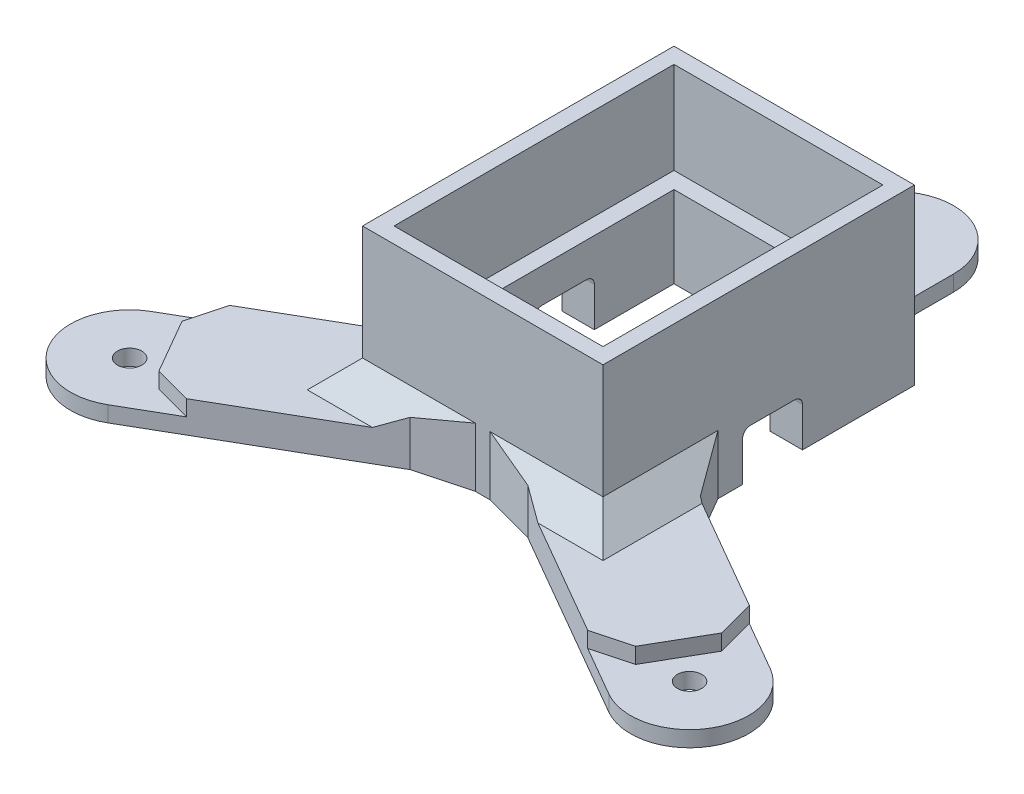
SolidWorks part; units mm, degrees
ref_plane "Front Plane" through (0, 0, 0) normal (0, 0, 1) x (1, 0, 0)
ref_plane "Top Plane" through (0, 0, 0) normal (0, 1, 0) x (1, 0, 0)
ref_plane "Right Plane" through (0, 0, 0) normal (1, 0, 0) x (0, 0, -1)
sketch "Sketch1" plane through (0, 0, 0) normal (0, 1, 0) x (1, 0, 0)
  line L0 (15.25, 19.75) -> (-15.25, 19.75)
  line L1 (13.25, -17.75) -> (-13.25, -17.75)
  line L2 (13.25, -17.75) -> (13.25, 17.75)
  line L3 (13.25, 17.75) -> (-13.25, 17.75)
  line L4 (-13.25, -17.75) -> (-13.25, 17.75)
  line L5 (13.25, -17.75) -> (-13.25, 17.75) construction
  line L6 (13.25, 17.75) -> (-13.25, -17.75) construction
  line L7 (-15.25, -19.75) -> (-15.25, 19.75)
  line L8 (15.25, -19.75) -> (-15.25, -19.75)
  line L9 (15.25, -19.75) -> (15.25, 19.75)
  point P0 (0, 0)
  dimension "D1" = 35.5
  dimension "D2" = 26.5
  dimension "D3" = 2
extrude "Boss-Extrude1" add sketch "Sketch1" along normal blind 22
sketch "Sketch3" plane through (0, 0, 0) normal (0, -1, 0) x (1, 0, 0)
  line L1 (-13.25, 17.75) -> (13.25, 17.75)
  line L2 (-13.25, 17.75) -> (-13.25, -17.75)
  line L3 (-13.25, -17.75) -> (13.25, -17.75)
  line L4 (13.25, 17.75) -> (13.25, -17.75)
  line L12 (-11.15, 15.65) -> (-11.15, -15.65)
  line L13 (11.15, 15.65) -> (-11.15, 15.65)
  line L14 (11.15, -15.65) -> (11.15, 15.65)
  line L15 (-11.15, -15.65) -> (11.15, -15.65)
  line L16 (-11.15, 15.65) -> (-11.15, -15.65)
  line L17 (11.15, 15.65) -> (-11.15, 15.65)
  line L18 (11.15, -15.65) -> (11.15, 15.65)
  line L19 (-11.15, -15.65) -> (11.15, -15.65)
  dimension "D1" = 2.1
extrude "Boss-Extrude3" add sketch "Sketch3" against normal blind 10.35
sketch "Sketch4" plane through (0, 22, 0) normal (0, 1, 0) x (1, 0, 0)
  line L1 (-15.25, 19.75) -> (-15.25, -19.75) construction
  line L2 (0, -8.53) -> (-35.507, -29.03) construction
  line L6 (-31.757, -35.5252) -> (-4.4336, -19.75)
  line L7 (-15.25, -19.75) -> (15.25, -19.75) construction
  line L10 (-15.25, -8.6743) -> (-39.257, -22.5348)
  line L11 (0, 0) -> (0, -8.53) construction
  line L12 (15.25, 19.75) -> (-15.25, 19.75) construction
  line L13 (-7.5, 19.75) -> (7.5, 19.75)
  line L14 (-7.5, 19.75) -> (-7.5, 32.47)
  line L15 (-7.5, 32.47) -> (7.5, 32.47) construction
  line L16 (7.5, 19.75) -> (7.5, 32.47)
  line L17 (-15.25, -8.6743) -> (-15.25, -19.75)
  line L19 (-15.25, -19.75) -> (-4.4336, -19.75)
  circle A1 centre (0, -8.53) radius 41 construction
  arc A3 (-7.5, 32.47) -> (7.5, 32.47) centre (0, 32.47) cw
  circle A4 centre (-35.507, -29.03) radius 1.55
  arc A6 (-39.257, -22.5348) -> (-31.757, -35.5252) centre (-35.507, -29.03) ccw
  circle A7 centre (0, 32.47) radius 1.55
  point P23 (0, 19.75)
  dimension "D1" = 120
  dimension "D2" = 82
  dimension "D4" = 15
  dimension "D5" = 3.1
  dimension "D3" = 8.53
  dimension "D6" = 15
extrude "Boss-Extrude4" add sketch "Sketch4" along normal blind 4 from surface starting at face at (0, 0, 0)
sketch "Sketch6" plane through (0, 4, 0) normal (0, 1, 0) x (1, 0, 0)
  line L1 (-2.85, 34.1154) -> (-2.85, 30.8246)
  line L2 (-2.85, 30.8246) -> (0, 29.1791)
  line L3 (0, 29.1791) -> (2.85, 30.8246)
  line L4 (2.85, 30.8246) -> (2.85, 34.1154)
  line L5 (2.85, 34.1154) -> (0, 35.7609)
  line L6 (0, 35.7609) -> (-2.85, 34.1154)
  line L7 (-35.507, -32.3209) -> (-32.657, -30.6754)
  line L8 (-32.657, -30.6754) -> (-32.657, -27.3846)
  line L9 (-32.657, -27.3846) -> (-35.507, -25.7391)
  line L10 (-35.507, -25.7391) -> (-38.357, -27.3846)
  line L11 (-38.357, -27.3846) -> (-38.357, -30.6754)
  line L12 (-38.357, -30.6754) -> (-35.507, -32.3209)
  circle A0 centre (0, 32.47) radius 2.85 construction
  circle A1 centre (-35.507, -29.03) radius 2.85 construction
  dimension "D1" = 5.7
extrude "Cut-Extrude1" cut sketch "Sketch6" against normal offset from surface (2 mm away) 2 up to face at (-7.4494, 0, -3.7687)
mirror "Mirror1" about plane through (0, 0, 0) normal (1, 0, 0) of "Cut-Extrude1", "Boss-Extrude4"
sketch "Sketch7" plane through (15.25, 0, 0) normal (1, 0, 0) x (0, 0, -1)
  line L0 (19.75, 22) -> (19.75, 0) construction
  line L1 (5.55, 0) -> (-2.05, 0)
  line L2 (5.55, 0) -> (5.55, 5)
  line L3 (4.55, 6) -> (-1.05, 6)
  line L4 (-2.05, 0) -> (-2.05, 5)
  line L6 (-8.6743, 0) -> (19.75, 0) construction
  line L7 (1.75, 6) -> (1.75, 0) construction
  arc A0 (5.55, 5) -> (4.55, 6) centre (4.55, 5) ccw
  arc A1 (-1.05, 6) -> (-2.05, 5) centre (-1.05, 5) ccw
  point P14 (5.55, 6)
  point P17 (-2.05, 6)
  dimension "D4" = 1
  dimension "D1" = 7.6
  dimension "D2" = 6
  dimension "D3" = 18
extrude "Cut-Extrude2" cut sketch "Sketch7" against normal through all
sketch "Sketch8" plane through (0, 4, 0) normal (0, 1, 0) x (1, 0, 0)
  line L0 (-35.974, -20.6394) -> (-28.474, -33.6297)
  line L1 (-15.25, -8.6743) -> (-39.257, -22.5348) construction
  line L2 (-31.757, -35.5252) -> (-4.4336, -19.75) construction
  line L3 (-35.974, -20.6394) -> (-39.257, -22.5348)
  line L4 (-31.757, -35.5252) -> (-28.474, -33.6297)
  line L5 (7.5, 19.75) -> (7.5, 32.47) construction
  line L6 (-7.5, 32.47) -> (-7.5, 19.75) construction
  line L7 (7.5, 28.6791) -> (7.5, 32.47)
  line L8 (-7.5, 32.47) -> (-7.5, 28.6791)
  line L9 (-7.5, 28.6791) -> (7.5, 28.6791)
  line L10 (0, 0) -> (0, 15.65) construction
  line L11 (-11.15, 15.65) -> (11.15, 15.65) construction
  line L12 (31.757, -35.5252) -> (28.474, -33.6297)
  line L13 (35.974, -20.6394) -> (39.257, -22.5348)
  line L14 (35.974, -20.6394) -> (28.474, -33.6297)
  arc A0 (-39.257, -22.5348) -> (-31.757, -35.5252) centre (-35.507, -29.03) ccw construction
  arc A1 (-39.257, -22.5348) -> (-31.757, -35.5252) centre (-35.507, -29.03) ccw
  arc A2 (7.5, 32.47) -> (-7.5, 32.47) centre (0, 32.47) ccw construction
  arc A3 (7.5, 32.47) -> (-7.5, 32.47) centre (0, 32.47) ccw
  arc A4 (39.257, -22.5348) -> (31.757, -35.5252) centre (35.507, -29.03) cw
  dimension "D1" = 0.5
  dimension "D2" = 0.5
extrude "Cut-Extrude3" cut sketch "Sketch8" against normal up to surface (2 mm away) up to face at (-35.507, 2, 30.58)
chamfer "Chamfer1" distance 3.5 distance2 3.5 6 edges at (7.5, 2, -19.75) (-7.5, 2, -19.75) (-15.25, 2, 8.6743) (-4.4336, 2, 19.75) (4.4336, 2, 19.75) (15.25, 2, 8.6743)
chamfer "Chamfer2" distance 3.5 distance2 3.5 6 edges at (-7.5, 3, -28.6791) (7.5, 3, -28.6791) (35.974, 3, 20.6394) (28.474, 3, 33.6297) (-28.474, 3, 33.6297) (-35.974, 3, 20.6394)
chamfer "Chamfer3" distance 3.5 distance2 3.5 5 edges at (15.25, 4, 12.4622) (8.0918, 4, 19.75) (-8.0918, 4, 19.75) (-15.25, 4, 12.4622) (0, 4, -19.75)
